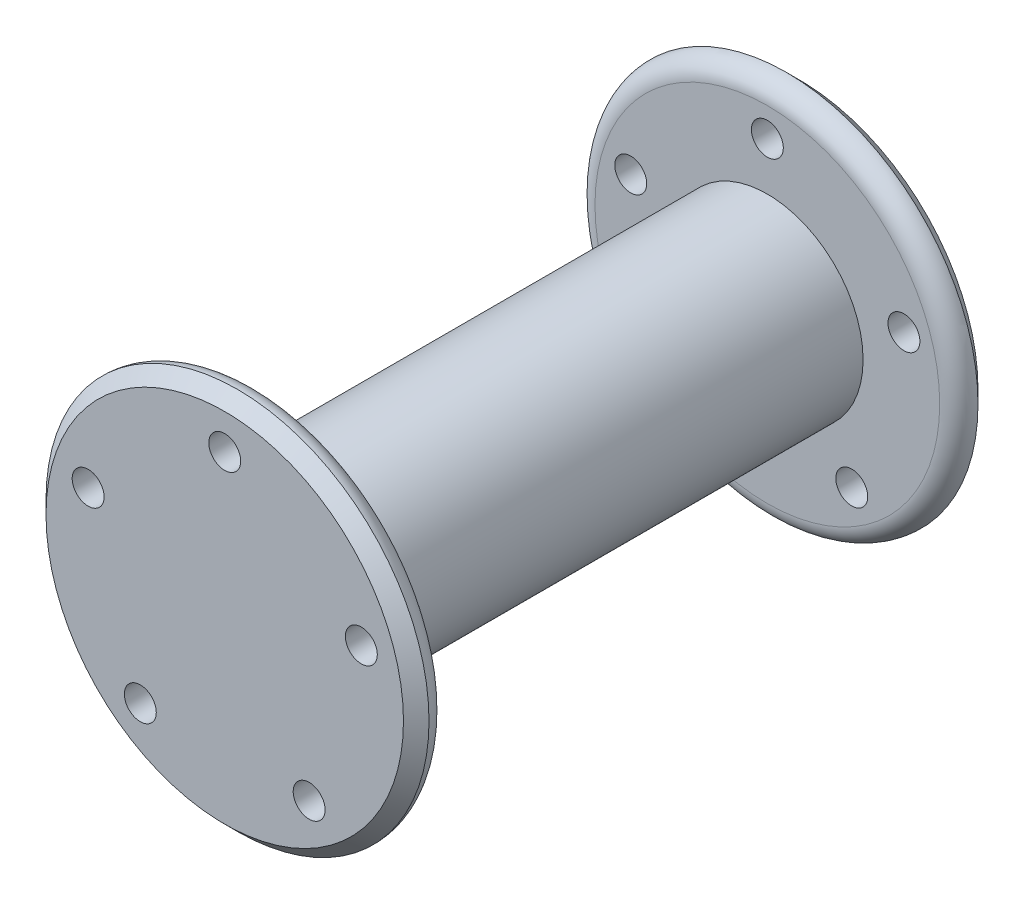
SolidWorks part; units mm, degrees
ref_plane "Front Plane" through (0, 0, 0) normal (0, 0, 1) x (1, 0, 0)
ref_plane "Top Plane" through (0, 0, 0) normal (0, 1, 0) x (1, 0, 0)
ref_plane "Right Plane" through (0, 0, 0) normal (1, 0, 0) x (0, 0, -1)
sketch "Sketch1" plane through (0, 0, 0) normal (0, 0, 1) x (1, 0, 0)
  circle A0 centre (0, 0) radius 15
  dimension "ShaftDiameter" = 30
extrude "Boss-Extrude1" add sketch "Sketch1" along normal mid plane 80
sketch "Sketch2" plane through (0, 0, -40) normal (0, 0, -1) x (-1, 0, 0)
  circle A0 centre (0, 0) radius 30
  dimension "CapDiameter" = 60
extrude "Boss-Extrude2" add sketch "Sketch2" along normal blind 5
chamfer "Chamfer1" distance 2 angle 45 1 edges at (-30, 0, -45)
hole_wizard "CBORE for #12 Binding Head Machine Screw1" [suppressed] positions "Sketch3" profile "Sketch4" counterbore size "#12" standard "ANSI Inch"
sketch "Sketch3" plane through (0, 0, -55) normal (0, 0, -1) x (-1, 0, 0)
  point P0 (0, 0)
sketch "Sketch4" plane through (0, 0, -55) normal (1, 0, 0) x (0, 1, 0)
  line L0 (0, 0) -> (0, 110)
  line L1 (0, 110) -> (2.8956, 110)
  line L3 (2.8956, 110) -> (2.8956, 3.5814)
  line L4 (5.9538, 3.5814) -> (2.8956, 3.5814)
  line L5 (5.9538, 3.5814) -> (5.9538, 0.635)
  line L6 (5.9538, 0.635) -> (6.5888, 0)
  line L7 (6.5888, 0) -> (0, 0)
  line L8 (-5.9538, 0.635) -> (-6.5888, 0) construction
  line L11 (0, -6.35) -> (0, 107.95) construction
  dimension "Thru Hole Dia." = 5.7912
  dimension "Thru Hole Depth" = 110
  dimension "C'Bore Dia." = 11.9075
  dimension "C'Bore Depth" = 3.5814
  dimension "Near C'Sink Dia." = 13.1775
  dimension "Near C'Sink Angle" = 90
sketch "Sketch5" plane through (0, 0, -45) normal (0, 0, -1) x (-1, 0, 0)
  line L0 (0, 15) -> (0, 30) construction
  circle A0 centre (0, 0) radius 15 construction
  circle A1 centre (0, 0) radius 30 construction
  circle A2 centre (0, 22.5) radius 2.5
extrude "Cut-Extrude1" cut sketch "Sketch5" against normal through all
pattern_circular "CirPattern1" count 5 over 360 about axis through (0, 0, 0) along (0, 0, 1) of "Cut-Extrude1"
fillet "Fillet1" radius 3 1 edges at (-30, 0, -40)
mirror "Mirror2" about plane through (0, 0, 0) normal (0, 0, 1) of "Fillet1", "CirPattern1", "Cut-Extrude1", "CBORE for #12 Binding Head Machine Screw1", "Chamfer1", "Boss-Extrude2"
